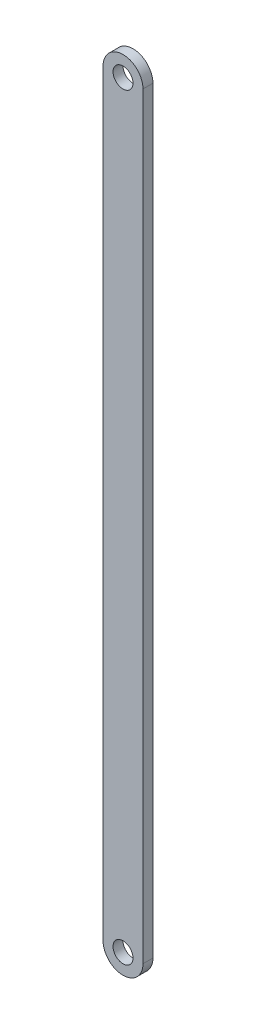
SolidWorks part; units mm, degrees
ref_plane "Front Plane" through (0, 0, 0) normal (0, 0, 1) x (1, 0, 0)
ref_plane "Top Plane" through (0, 0, 0) normal (0, 1, 0) x (1, 0, 0)
ref_plane "Right Plane" through (0, 0, 0) normal (1, 0, 0) x (0, 0, -1)
sketch "Sketch1" plane through (0, 0, 0) normal (0, 0, 1) x (1, 0, 0)
  line L0 (12.7, -241.3) -> (12.7, 241.3)
  line L1 (-12.7, -241.3) -> (-12.7, 241.3)
  line L2 (-202.6736, 254) -> (202.6736, 254) construction
  line L3 (-97.76, 0) -> (97.76, 0) construction
  arc A0 (-12.7, 241.3) -> (12.7, 241.3) centre (0, 241.3) cw
  circle A1 centre (0, 241.3) radius 6.35
  circle A2 centre (0, -241.3) radius 6.35
  arc A3 (-12.7, -241.3) -> (12.7, -241.3) centre (0, -241.3) ccw
  point P2 (12.7, 0)
  point P9 (0, 254)
  point P10 (0, 0)
  point P17 (-12.7, 0)
  dimension "D3" = 12.7
  dimension "D1" = 241.3
  dimension "D2" = 12.7
extrude "Boss-Extrude1" add sketch "Sketch1" along normal blind 6.35
